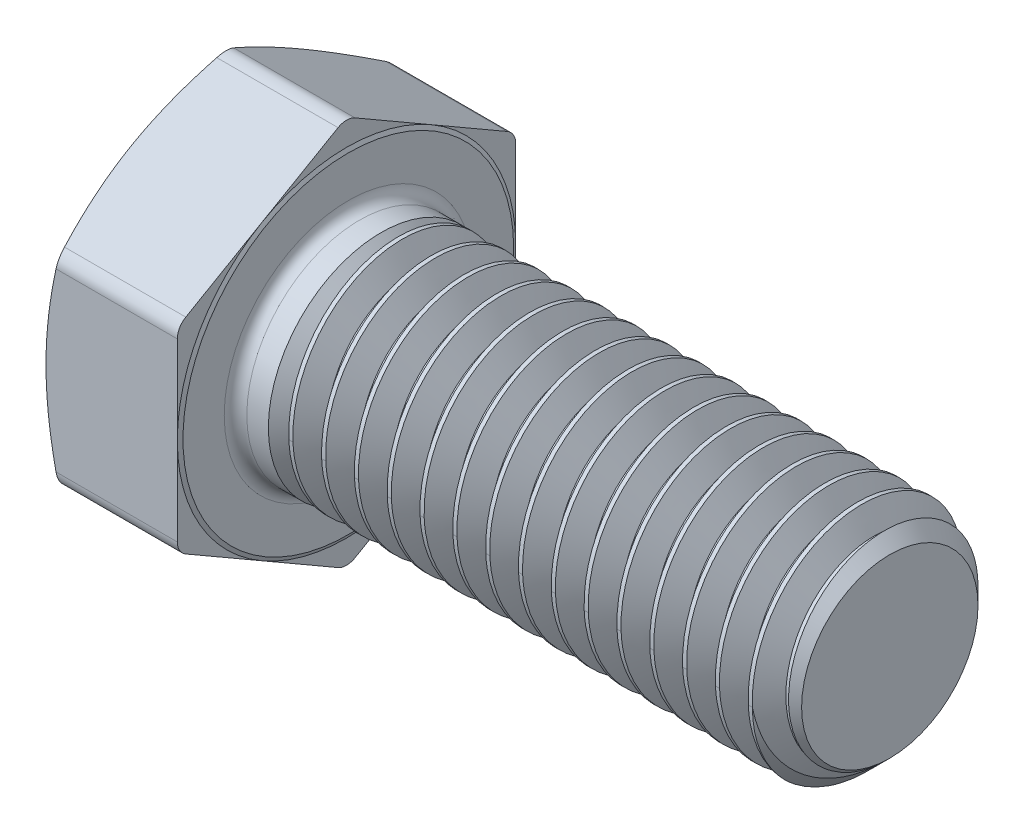
SolidWorks part; units mm, degrees
ref_plane "Front Plane" through (0, 0, 0) normal (0, 0, 1) x (1, 0, 0)
ref_plane "Top Plane" through (0, 0, 0) normal (0, 1, 0) x (1, 0, 0)
ref_plane "Right Plane" through (0, 0, 0) normal (1, 0, 0) x (0, 0, -1)
sketch "Sketch1" plane through (0, 0, 0) normal (0, 0, 1) x (1, 0, 0)
  line L0 (0, 0) -> (38.1, 0) construction
  line L1 (0, 0) -> (-9.9219, 0) construction
  line L2 (0, 11.9062) -> (0, -11.9062) construction
  line L3 (-9.9219, 11.9062) -> (-9.9219, -11.9063) construction
  line L4 (38.1, 7.9375) -> (38.1, -7.9375) construction
  line L8 (35.7909, 7.9375) -> (38.1, 7.9375) construction
  point P8 (35.7909, 0)
  point P11 (30.0182, -7.9375)
  point P12 (2.3091, 0)
  dimension "Head Height" = 9.9219
  dimension "Head Width" = 23.8125
  dimension "Length" = 38.1
  dimension "Thread Size" = 15.875
  dimension "D1" = 8.0818
  dimension "Thread Pitch" = 2.3091
  dimension "D2" = 2.3091
sketch "Sketch2" plane through (0, 0, 0) normal (1, 0, 0) x (0, 0, -1)
  circle A0 centre (0, 0) radius 7.9375
extrude "Boss-Extrude1" add sketch "Sketch2" along normal up to vertex (38.1 mm away) up to point (38.1, 7.9375, 0)
sketch "Sketch3" plane through (0, 0, 0) normal (-1, 0, 0) x (0, 0, 1)
  line L0 (0, 13.7482) -> (0, 0) construction
  line L1 (0, 13.7482) -> (-11.9062, 6.8741)
  line L2 (-11.9062, 6.8741) -> (-11.9062, -6.8741)
  line L3 (-11.9062, -6.8741) -> (0, -13.7482)
  line L4 (0, -13.7482) -> (11.9062, -6.8741)
  line L5 (11.9062, -6.8741) -> (11.9062, 6.8741)
  line L6 (11.9062, 6.8741) -> (0, 13.7482)
  circle A0 centre (0, 0) radius 11.9062 construction
extrude "Boss-Extrude2" add sketch "Sketch3" along normal up to vertex (9.9219 mm away) up to point (-9.9219, 11.9062, 0)
sketch "Sketch5" plane through (-9.9219, 0, 0) normal (-1, 0, 0) x (0, 0, 1)
  circle A0 centre (0, 0) radius 11.9062 construction
  circle A1 centre (0, 0) radius 11.9062 construction
  circle A2 centre (0, 0) radius 10.7156
  dimension "D1" = 1.1906
extrude "Cut-Extrude1" cut sketch "Sketch5" against normal up to vertex (9.9219 mm away) draft 65 flip side to cut up to point (0, 0, 0)
sketch "Sketch11" plane through (-9.9219, 0, 0) normal (-1, 0, 0) x (0, 0, 1)
  line L0 (0, 8.4534) -> (0, 5.2388) construction
  line L1 (0.4762, 8.4534) -> (0.4762, 5.2388)
  line L2 (-0.4763, 8.4534) -> (-0.4763, 5.2388)
  arc A0 (0.4762, 8.4534) -> (-0.4763, 8.4534) centre (0, 8.4534) ccw
  arc A1 (-0.4763, 5.2388) -> (0.4762, 5.2388) centre (0, 5.2388) ccw
  circle A2 centre (0, 0) radius 8.9297 construction
  circle A3 centre (0, 0) radius 4.7625 construction
  point P3 (0, 6.8461)
  dimension "D1" = 17.8594
  dimension "D2" = 9.525
  dimension "D3" = 0.9525
extrude "Boss-Extrude5" add sketch "Sketch11" along normal blind 0.0635
fillet "Fillet5" radius 0.0635 4 edges at (-9.9854, 6.8461, 0.4762) (-9.9854, 4.7625, 0) (-9.9854, 6.8461, -0.4763) (-9.9854, 8.9297, 0)
pattern_circular "CirPattern1" count 6 over 360 about axis through (0, 0, 0) along (-1, 0, 0) of "Boss-Extrude5", "Fillet5" reverse direction yes
fillet "Fillet7" radius 1.1906 6 edges at (-4.2539, -13.7482, 0) (-4.2539, -6.8741, -11.9062) (-4.2539, 6.8741, -11.9062) (-4.2539, 13.7482, 0) (-4.2539, -6.8741, 11.9062) (-4.2539, 6.8741, 11.9062)
chamfer "Chamfer1" distance 1.7318 angle 45 1 edges at (38.1, 0, -7.9375)
sketch "Sketch15" plane through (0, 0, 0) normal (0, 0, 1) x (1, 0, 0)
  line L0 (0, 11.6339) -> (-0.127, 11.9062)
  line L1 (0, 11.9062) -> (0, -11.9062) construction
  line L2 (-0.127, 11.9062) -> (-0.127, 13.7482)
  line L3 (-0.127, 13.7482) -> (0, 13.7482)
  line L4 (0, 13.7482) -> (0, 11.6339)
  dimension "D1" = 0.127
  dimension "D2" = 25
revolve "Cut-Revolve1" cut sketch "Sketch15" angle 360 about L1
fillet "Fillet4" radius 0.7937 1 edges at (0, 0, 7.9375)
sketch "Reference Sketch1" plane through (0, 0, 0) normal (1, 0, 0) x (0, 0, -1)
  line L1 (0, 13.7482) -> (-11.9062, 6.8741)
  line L2 (-11.9062, 6.8741) -> (-11.9063, -6.8741)
  line L3 (-11.9063, -6.8741) -> (0, -13.7482)
  line L4 (0, -13.7482) -> (11.9062, -6.8741)
  line L5 (11.9062, -6.8741) -> (11.9063, 6.8741)
  line L6 (11.9063, 6.8741) -> (0, 13.7482)
  circle A0 centre (0, 0) radius 11.9062 construction
  circle A1 centre (0, 0) radius 11.9062
sketch "Sketch12" plane through (38.1, 0, 0) normal (1, 0, 0) x (0, 0, -1)
  circle A1 centre (0, 0) radius 7.9375
ref_plane "Plane2" through (2.3091, 0, 0) normal (1, 0, 0) x (0, 0, -1)
split "Split1" trim tools "Plane2" bodies to split 126 116 resulting bodies 118 119
curve "Helix/Spiral2" pitch 2.3091 height 40.4091 radius 7.9375 centre (38.1, 0, 0) axis (-1, 0, 0) start towards (0, 1, 0) parameters "Pitch"=2.3091
sketch "Sketch13" plane through (0, 0, 0) normal (0, 0, 1) x (1, 0, 0)
  line L0 (37.9557, 8.1875) -> (39.1102, 6.1877) construction
  line L1 (39.1102, 6.1877) -> (40.2648, 8.1875) construction
  line L2 (40.2648, 8.1875) -> (37.9557, 8.1875) construction
  line L3 (39.1102, 6.1877) -> (39.1102, 6.4377) construction
  line L4 (38.1, 7.9375) -> (40.1205, 7.9375)
  line L5 (39.1102, 7.9375) -> (39.1102, 8.1875) construction
  line L6 (40.1205, 7.9375) -> (39.2545, 6.4377)
  line L7 (39.2545, 6.4377) -> (38.9659, 6.4377)
  line L8 (38.9659, 6.4377) -> (38.1, 7.9375)
  line L9 (35.7909, 7.9375) -> (38.1, 7.9375) construction
  dimension "D1" = 0.2886
sweep "Cut-Sweep1" cut profiles "Sketch13" path "Helix/Spiral2" align with end faces yes
sketch "Sketch14" plane through (2.3091, 0, 0) normal (1, 0, 0) x (0, 0, -1)
  circle A1 centre (0, 0) radius 7.9375
  circle A2 centre (0, 0) radius 7.9375
  dimension "D1" = 0
extrude "Boss-Extrude4" add sketch "Sketch14" along normal through all draft 50
equation "\"D1@Sketch11\"=\"Head Width@Sketch1\" * 0.75"
equation "\"D2@Sketch11\"=\"Head Width@Sketch1\"*0.4"
equation "\"D3@Sketch11\"=\"Head Width@Sketch1\" * .04"
equation "\"D3@Helix/Spiral2\"=\"Length@Sketch1\" + \"Thread Pitch@Sketch1\""
equation "\"D1@Chamfer1\"=\"Thread Pitch@Sketch1\"*0.750"
equation "\"D1@Sketch1\"=\"Thread Pitch@Sketch1\"*3.5"
equation "\"Pitch@Helix/Spiral2\"=\"Thread Pitch@Sketch1\""
equation "\"D1@Sketch13\"=\"Thread Pitch@Sketch1\"*0.125"
equation "\"D1@Sketch5\"=\"Head Width@Sketch1\"*0.05"
equation "\"D1@Fillet4\"=\"Thread Size@Sketch1\"*0.05"
equation "\"D2@Sketch1\"=\"Thread Pitch@Sketch1\""
equation "\"D1@Fillet7\"=\"Head Width@Sketch1\"*0.05"
